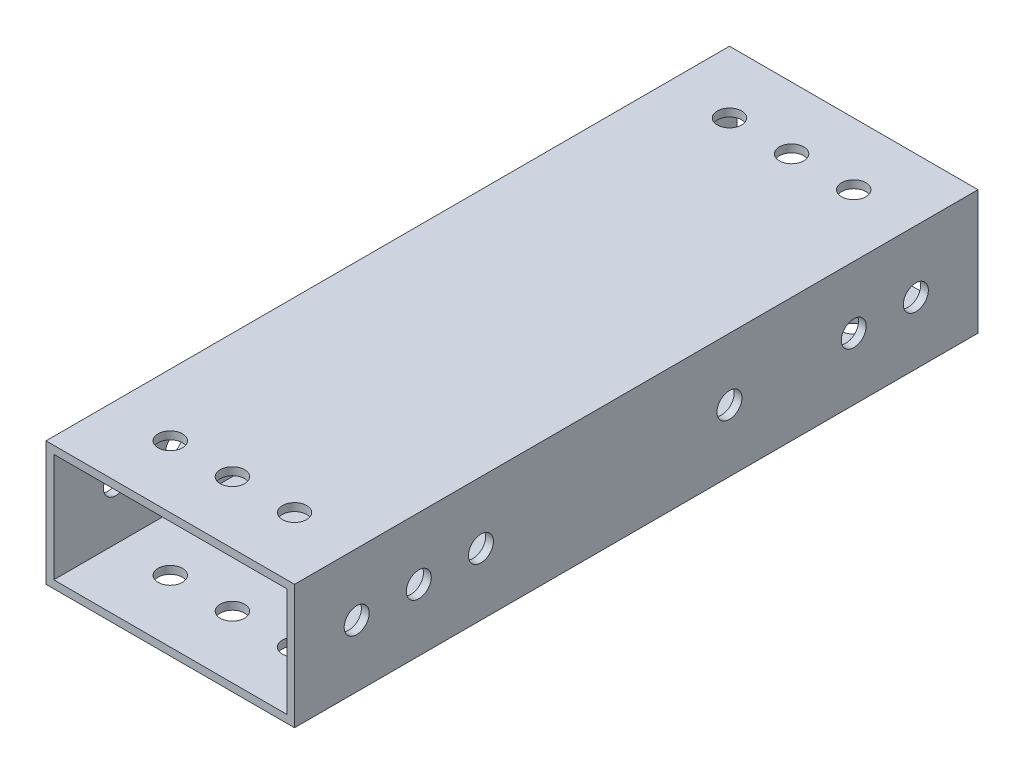
SolidWorks part; units mm, degrees
material "6061-T6 (SS)"
ref_plane "Front Plane" through (0, 0, 0) normal (0, 0, 1) x (1, 0, 0)
ref_plane "Top Plane" through (0, 0, 0) normal (0, 1, 0) x (1, 0, 0)
ref_plane "Right Plane" through (0, 0, 0) normal (1, 0, 0) x (0, 0, -1)
sketch "Sketch1" plane through (0, 0, 0) normal (0, 0, 1) x (1, 0, 0)
  line L0 (-23.8125, 11.1125) -> (23.8125, 11.1125)
  line L1 (-25.4, -12.7) -> (25.4, -12.7)
  line L2 (-25.4, -12.7) -> (-25.4, 12.7)
  line L3 (-25.4, 12.7) -> (25.4, 12.7)
  line L4 (25.4, -12.7) -> (25.4, 12.7)
  line L5 (-25.4, -12.7) -> (25.4, 12.7) construction
  line L6 (-25.4, 12.7) -> (25.4, -12.7) construction
  line L7 (23.8125, -11.1125) -> (23.8125, 11.1125)
  line L8 (-23.8125, -11.1125) -> (23.8125, -11.1125)
  line L9 (-23.8125, -11.1125) -> (-23.8125, 11.1125)
  point P0 (0, 0)
  dimension "D1" = 50.8
  dimension "D2" = 25.4
  dimension "D3" = 1.5875
extrude "Boss-Extrude1" add sketch "Sketch1" along normal mid plane 139.7
sketch "Sketch2" plane through (0, 12.7, 0) normal (0, 1, 0) x (1, 0, 0)
  line L0 (25.4, 69.85) -> (-25.4, 69.85) construction
  line L1 (25.4, 0) -> (-25.4, 0) construction
  line L2 (25.4, -69.85) -> (25.4, 69.85) construction
  line L3 (-25.4, -69.85) -> (-25.4, 69.85) construction
  circle A0 centre (-12.7, 57.15) radius 2.4892
  circle A1 centre (0, 57.15) radius 2.4892
  circle A2 centre (12.7, 57.15) radius 2.4892
  circle A3 centre (12.7, -57.15) radius 2.4892
  circle A4 centre (0, -57.15) radius 2.4892
  circle A5 centre (-12.7, -57.15) radius 2.4892
  dimension "D4" = 4.9784
  dimension "D1" = 12.7
  dimension "D2" = 12.7
  dimension "D3" = 12.7
extrude "Cut-Extrude1" cut sketch "Sketch2" against normal through all
sketch "Sketch3" plane through (-25.4, 0, 0) normal (-1, 0, 0) x (0, 0, 1)
  line L0 (-69.85, 12.7) -> (-69.85, -12.7) construction
  line L1 (0, 12.7) -> (0, -12.7) construction
  line L2 (69.85, 12.7) -> (-69.85, 12.7) construction
  line L3 (69.85, -12.7) -> (-69.85, -12.7) construction
  circle A0 centre (-57.15, 0) radius 2.5527
  circle A1 centre (57.15, 0) radius 2.5527
  circle A4 centre (31.75, 0) radius 2.5527
  circle A5 centre (44.45, 0) radius 2.5527
  dimension "D1" = 5.1054
  dimension "D3" = 12.7
  dimension "D4" = 12.7
  dimension "D2" = 12.7
extrude "Cut-Extrude2" cut sketch "Sketch3" against normal through all contours A5 | A1 | A4 | A0
sketch "Sketch5" plane through (25.4, 0, 0) normal (1, 0, 0) x (0, 0, -1)
  line L0 (69.85, -12.7) -> (69.85, 12.7) construction
  circle A1 centre (44.45, 0) radius 2.5527
  circle A2 centre (19.05, 0) radius 2.5527
  dimension "D1" = 25.4
  dimension "D3" = 5.1054
  dimension "D4" = 25.4
extrude "Cut-Extrude3" cut sketch "Sketch5" against normal through all
